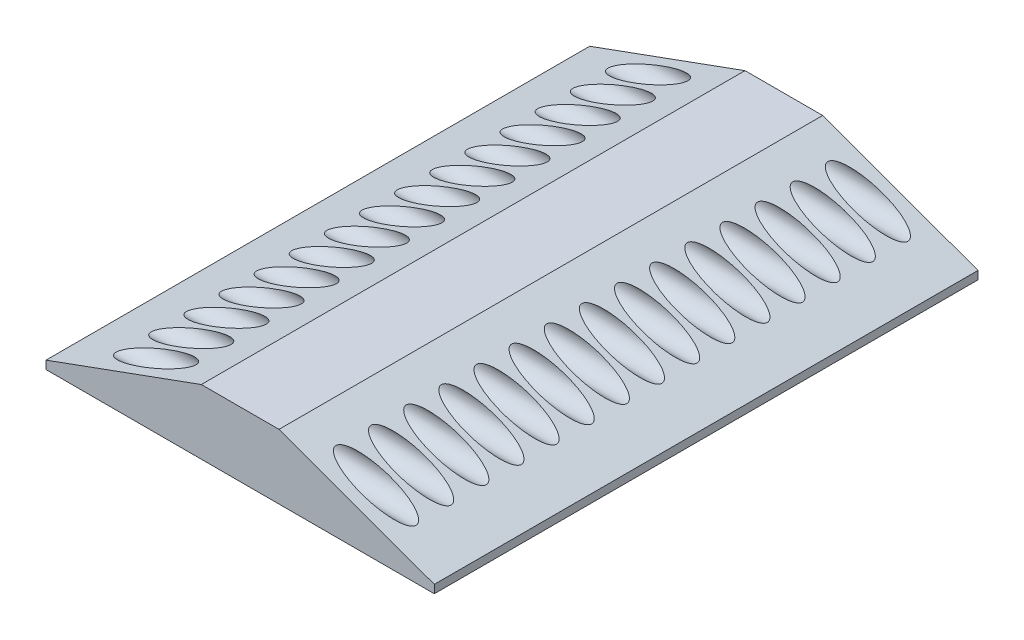
SolidWorks part; units mm, degrees
ref_plane "Front Plane" through (0, 0, 0) normal (0, 0, 1) x (1, 0, 0)
ref_plane "Top Plane" through (0, 0, 0) normal (0, 1, 0) x (1, 0, 0)
ref_plane "Right Plane" through (0, 0, 0) normal (1, 0, 0) x (0, 0, -1)
sketch "Sketch1" plane through (0, 0, 0) normal (0, 1, 0) x (1, 0, 0)
  line L1 (-15, -21) -> (15, -21)
  line L2 (-15, -21) -> (-15, 21)
  line L3 (-15, 21) -> (15, 21)
  line L4 (15, -21) -> (15, 21)
  line L5 (-15, -21) -> (15, 21) construction
  line L6 (-15, 21) -> (15, -21) construction
  point P0 (0, 0)
  dimension "D1" = 42
  dimension "D2" = 30
extrude "Boss-Extrude1" add sketch "Sketch1" along normal blind 5
sketch "Sketch2" plane through (15, 0, 0) normal (1, 0, 0) x (0, 0, -1)
  line L0 (-21, 3) -> (21, 3) construction
  line L1 (-21, 5) -> (-21, 0) construction
  line L2 (21, 5) -> (21, 0) construction
  line L3 (-21, 5) -> (21, 5) construction
  circle A0 centre (-19, 3) radius 1.125
  circle A1 centre (-16.2857, 3) radius 1.125
  circle A2 centre (-13.5714, 3) radius 1.125
  circle A3 centre (-10.8571, 3) radius 1.125
  circle A4 centre (-8.1429, 3) radius 1.125
  circle A5 centre (-5.4286, 3) radius 1.125
  circle A6 centre (-2.7143, 3) radius 1.125
  circle A7 centre (0, 3) radius 1.125
  circle A8 centre (2.7143, 3) radius 1.125
  circle A9 centre (5.4286, 3) radius 1.125
  circle A10 centre (8.1429, 3) radius 1.125
  circle A11 centre (10.8571, 3) radius 1.125
  circle A12 centre (13.5714, 3) radius 1.125
  circle A13 centre (16.2857, 3) radius 1.125
  circle A14 centre (19, 3) radius 1.125
  point P10 (19.1107, 8)
  dimension "D5" = 2.25
  dimension "D1" = 2
  dimension "D3" = 2
  dimension "D4" = 2
  dimension "D2" = 15
extrude "Cut-Extrude1" cut sketch "Sketch2" against normal through all
chamfer "Chamfer1" distance 12 angle 20 1 edges at (15, 5, 0) first distance on face at (0, 5, 0)
chamfer "Chamfer2" distance 12 angle 20 1 edges at (-15, 5, 0) first distance on face at (-6, 5, 0)
